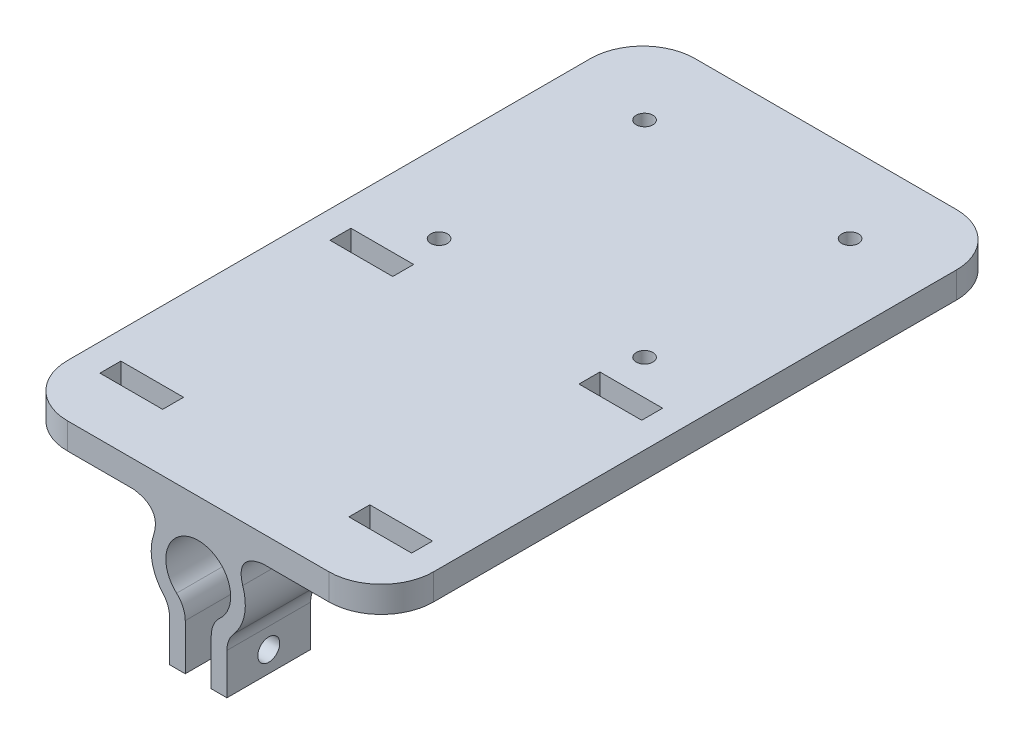
SolidWorks part; units mm, degrees
ref_plane "Front Plane" through (0, 0, 0) normal (0, 0, 1) x (1, 0, 0)
ref_plane "Top Plane" through (0, 0, 0) normal (0, 1, 0) x (1, 0, 0)
ref_plane "Right Plane" through (0, 0, 0) normal (1, 0, 0) x (0, 0, -1)
sketch "Sketch3" plane through (0, 0, 0) normal (0, 0, 1) x (1, 0, 0)
  line L0 (0, 11) -> (0, 0) construction
  line L1 (-35, 13.5) -> (35, 13.5)
  line L2 (-35, 13.5) -> (-35, 8.5)
  line L3 (-35, 8.5) -> (35, 8.5)
  line L4 (35, 13.5) -> (35, 8.5)
  line L5 (-35, 13.5) -> (35, 8.5) construction
  line L6 (-35, 8.5) -> (35, 13.5) construction
  point P0 (0, 11)
  dimension "D1" = 5
  dimension "D2" = 70
  dimension "D3" = 11
extrude "Boss-Extrude2" add sketch "Sketch3" along normal blind 120 from offset 10
sketch "Sketch1" plane through (0, 0, 0) normal (0, 0, 1) x (1, 0, 0)
  line L0 (-35, 8.5) -> (35, 8.5) construction
  line L1 (0, 0) -> (0, -9) construction
  line L2 (-12.3518, 8.5) -> (12.3518, 8.5)
  line L3 (0, 0) -> (-5.4853, -7.1352) construction
  line L5 (2.4853, -17.1352) -> (2.4853, -8.3313)
  line L6 (-3.9853, -17.1352) -> (-2.4853, -17.1352)
  line L7 (-3.9853, -17.1352) -> (-5.4853, -17.1352)
  line L8 (-2.4853, -17.1352) -> (-2.4853, -8.3313)
  line L9 (-5.4853, -17.1352) -> (-5.4853, -9.2768)
  line L10 (3.9853, -17.1352) -> (5.4853, -17.1352)
  line L11 (3.9853, -17.1352) -> (2.4853, -17.1352)
  line L12 (5.4853, -17.1352) -> (5.4853, -9.2768)
  arc A0 (4.1436, -4.612) -> (-4.1436, -4.612) centre (0, 0) ccw
  arc A1 (6.7405, -5.9637) -> (8.4982, 2.9632) centre (0, 0) ccw
  arc A2 (-5.4853, -9.2768) -> (-6.7405, -5.9637) centre (-10.4853, -9.2768) ccw
  arc A3 (-2.4853, -8.3313) -> (-4.1436, -4.612) centre (-7.4853, -8.3313) ccw
  arc A4 (2.4853, -8.3313) -> (4.1436, -4.612) centre (7.4853, -8.3313) cw
  arc A5 (5.4853, -9.2768) -> (6.7405, -5.9637) centre (10.4853, -9.2768) cw
  arc A6 (-8.4982, 2.9632) -> (-6.7405, -5.9637) centre (0, 0) ccw
  spline S0 degree 3 poles (-12.3518, 8.5) (-9.9792, 8.1529) (-7.3004, 7.013) (-8.4982, 2.9632) knots 0 0 0 0 1 1 1 1
  spline S1 degree 3 poles (12.3518, 8.5) (9.9792, 8.1529) (7.3004, 7.013) (8.4982, 2.9632) knots 0 0 0 0 1 1 1 1
  point P18 (-2.4853, -5.6801)
  point P21 (2.4853, -5.6801)
  point P24 (5.4853, -7.1352)
  dimension "D1" = 12.4
  dimension "D2" = 18
  dimension "D6" = 1.5
  dimension "D3" = 5
  dimension "D4" = 5
  dimension "D10" = 5
  dimension "D11" = 5
  dimension "D5" = 37.552
  dimension "D7" = 1.5
  dimension "D8" = 10
  dimension "D9" = 11.4552
extrude "Boss-Extrude3" add sketch "Sketch1" along normal blind 8 and the other way blind 8 from offset 18
ref_plane "Plane4" through (0, 0, 70) normal (0, 0, 1) x (1, 0, 0)
sketch "Sketch4" plane through (-5.4853, 0, 0) normal (-1, 0, 0) x (0, 0, 1)
  line L0 (10, -9.2768) -> (26, -16.9992) construction
  line L1 (26, -9.2768) -> (26, -17.1352) construction
  circle A0 centre (18, -13.138) radius 2.1
  dimension "D1" = 4.2
extrude "Cut-Extrude1" cut sketch "Sketch4" against normal blind 11
mirror "Mirror2" about plane through (0, 0, 70) normal (0, 0, 1) of "Boss-Extrude3", "Cut-Extrude1"
sketch "Sketch5" plane through (0, 13.5, 0) normal (0, 1, 0) x (1, 0, 0)
  line L0 (-16.8494, -70) -> (16.8494, -70) construction
  line L1 (-19.65, -25) -> (19.65, -25) construction
  line L2 (-19.65, -25) -> (-19.65, -64.3) construction
  line L3 (-19.65, -64.3) -> (19.65, -64.3) construction
  line L4 (19.65, -25) -> (19.65, -64.3) construction
  line L5 (-19.65, -25) -> (19.65, -64.3) construction
  line L6 (-19.65, -64.3) -> (19.65, -25) construction
  line L8 (35, -10) -> (-35, -130) construction
  line L9 (-35, -10) -> (-35, -130) construction
  line L10 (35, -130) -> (-35, -130) construction
  line L11 (35, -10) -> (-35, -10) construction
  line L18 (0, -10) -> (0, -130) construction
  circle A0 centre (19.65, -25) radius 1.6
  circle A1 centre (19.65, -64.3) radius 1.6
  circle A2 centre (-19.65, -64.3) radius 1.6
  circle A3 centre (-19.65, -25) radius 1.6
  point P0 (0, -70)
  point P23 (0, -44.65)
  dimension "D3" = 3.2
  dimension "D4" = 15
  dimension "D1" = 39.3
  dimension "D2" = 39.3
sketch "Sketch6" plane through (0, 13.5, 0) normal (0, 1, 0) x (1, 0, 0)
  line L0 (-16.8494, -70) -> (16.8494, -70) construction
  line L1 (-29.8063, -75) -> (-17.8063, -75)
  line L2 (-29.8063, -75) -> (-29.8063, -115) construction
  line L3 (-29.8063, -115) -> (-17.8063, -115)
  line L4 (29.8063, -75) -> (29.8063, -115) construction
  line L5 (-29.8063, -75) -> (29.8063, -115) construction
  line L6 (-29.8063, -115) -> (29.8063, -75) construction
  line L7 (-17.8063, -71) -> (-17.8063, -75)
  line L8 (17.8063, -71) -> (17.8063, -75)
  line L9 (-29.8063, -75) -> (-29.8063, -71)
  line L10 (-29.8063, -71) -> (-17.8063, -71)
  line L11 (29.8063, -71) -> (29.8063, -97.085)
  line L12 (-29.8063, -115) -> (-29.8063, -119)
  line L13 (-29.8063, -119) -> (-17.8063, -119)
  line L14 (29.8063, -119) -> (29.8063, -115)
  line L15 (29.8063, -75) -> (29.8063, -97.085)
  line L16 (17.8063, -75) -> (29.8063, -75)
  line L17 (17.8063, -71) -> (29.8063, -71)
  line L18 (17.8063, -115) -> (29.8063, -115)
  line L19 (17.8063, -119) -> (29.8063, -119)
  line L20 (-17.8063, -115) -> (-17.8063, -119)
  line L21 (17.8063, -115) -> (17.8063, -119)
  point P0 (0, -95)
  dimension "D1" = 40
  dimension "D2" = 12
  dimension "D3" = 25
  dimension "D4" = 12
  dimension "D5" = 4
  dimension "D6" = 4
fillet "Fillet1" radius 10 4 edges at (35, 11, 10) (35, 11, 130) (-35, 11, 130) (-35, 11, 10)
extrude "Cut-Extrude2" cut sketch "Sketch5" against normal blind 11
extrude "Cut-Extrude6" cut sketch "Sketch6" against normal up to next contours L11 L10 L9 L1 | L13 L14 L3 L12 | L18 L21 L19 L14 | L17 L8 L16 L11 region at (-23.8063, 13.5, 73) region at (-23.8063, 13.5, 117) region at (23.8063, 13.5, 73) region at (23.8063, 13.5, 117)
